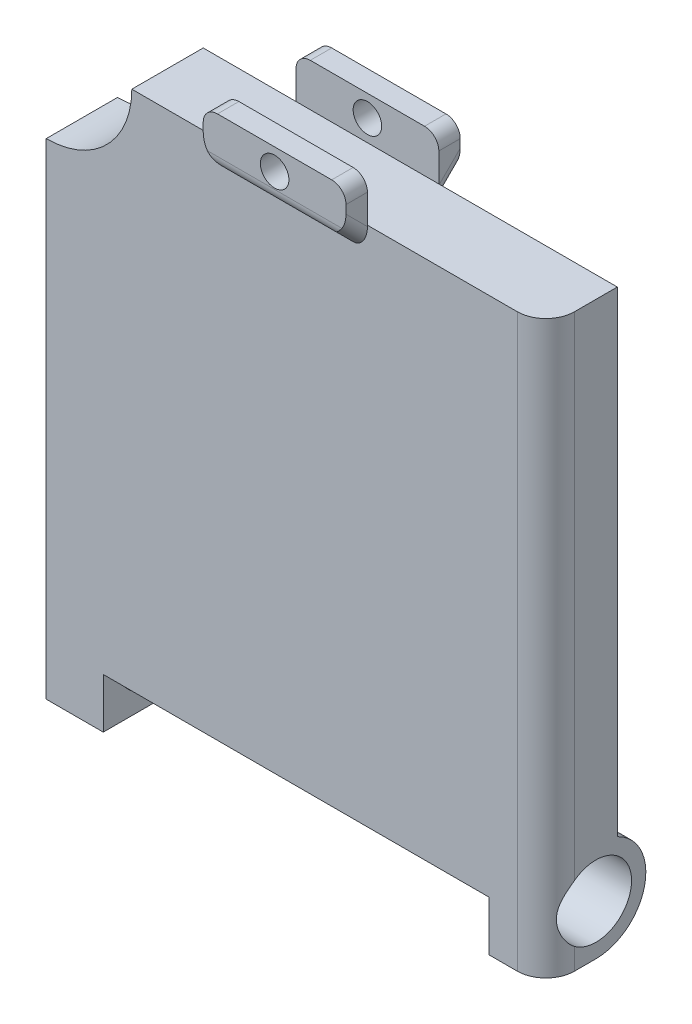
SolidWorks part; units mm, degrees
ref_plane "Front Plane" through (0, 0, 0) normal (0, 0, 1) x (1, 0, 0)
ref_plane "Top Plane" through (0, 0, 0) normal (0, 1, 0) x (1, 0, 0)
ref_plane "Right Plane" through (0, 0, 0) normal (1, 0, 0) x (0, 0, -1)
sketch "Sketch1" plane through (0, 0, 0) normal (0, 0, 1) x (1, 0, 0)
  line L0 (0, 0) -> (0, 36.5)
  line L1 (0, 36.5) -> (35, 36.5)
  line L2 (35, 36.5) -> (35, 0)
  line L3 (35, 0) -> (0, 0)
  dimension "D1" = 36.5
  dimension "D2" = 35
extrude "Boss-Extrude1" add sketch "Sketch1" along normal mid plane 5
sketch "Sketch3" plane through (35, 0, 0) normal (1, 0, 0) x (0, 0, -1)
  line L0 (-2.5, 5.8058) -> (-2.5, 2.251) construction
  line L2 (-2.5, 0) -> (-2.5, 36.5) construction
  line L3 (-2.5, 0) -> (2.5, 0) construction
  circle A0 centre (1, 0) radius 3.5
  dimension "D1" = 7
extrude "Cut-Extrude1" cut sketch "Sketch3" against normal up to surface (35 mm away) up to face at (0, 18.25, 0)
sketch "Sketch4" plane through (35, 0, 0) normal (1, 0, 0) x (0, 0, -1)
  line L0 (-2.5, 0) -> (-2.5, -3.5)
  line L1 (-2.5, -3.5) -> (1, -3.5)
  circle A0 centre (1, 0) radius 3.5
  arc A1 (2.5, 3.1623) -> (-2.5, 0) centre (1, 0) ccw construction
  circle A2 centre (1, 0) radius 2.5
  arc M4 (-2.5, 0) -> (2.5, 3.1623) centre (1, 0) cw
  dimension "D1" = 5
extrude "Boss-Extrude3" add sketch "Sketch4" against normal blind 4 contours A0 A2 M4 | A0 L0 L1 region at (35, -2.7182, 1.7182) region at (35, 2.8744, 0.8179)
ref_plane "Plane2" through (17.5, 0, 0) normal (1, 0, 0) x (0, 0, -1)
mirror "Mirror2" about plane through (17.5, 0, 0) normal (1, 0, 0) of "Boss-Extrude3"
sketch "Sketch5" plane through (17.5, 0, 0) normal (1, 0, 0) x (0, 0, -1)
  line L0 (2.5, 36.5) -> (4, 36.5)
  line L1 (-2.5, 36.5) -> (-4, 36.5)
  line L2 (-4, 36.5) -> (-2.5, 35)
  line L3 (-2.5, -3.5) -> (-2.5, 36.5) construction
  line L4 (4, 36.5) -> (2.5, 35)
  line L5 (2.5, 3.1623) -> (2.5, 36.5) construction
  line L6 (-4, 36.5) -> (-4, 39.5)
  line L7 (-4, 39.5) -> (-2.5, 39.5)
  line L8 (-2.5, 39.5) -> (-2.5, 36.5)
  line L9 (2.5, 36.5) -> (2.5, 39.5)
  line L10 (2.5, 39.5) -> (4, 39.5)
  line L11 (4, 39.5) -> (4, 36.5)
  line L12 (-2.5, 35) -> (-2.5, 36.5)
  line L13 (2.5, 35) -> (2.5, 36.5)
  dimension "D1" = 1.5
  dimension "D2" = 3
extrude "Boss-Extrude4" add sketch "Sketch5" along normal mid plane 10 contours L8 L7 L6 L1 | L2 L12 L1 | L13 L4 L0 | L11 L10 L9 L0 region at (17.5, 38, -3.25) region at (17.5, 36, -3) region at (17.5, 36, 3) region at (17.5, 38, 3.25)
sketch "Sketch6" plane through (0, 0, 4) normal (0, 0, 1) x (1, 0, 0)
  line L0 (17.5, 39.5) -> (17.5, 36.5) construction
  line L1 (22.5, 39.5) -> (12.5, 39.5) construction
  line L2 (22.5, 36.5) -> (12.5, 36.5) construction
  circle A0 centre (17.5, 38) radius 1
  point P8 (17.5, 38)
  dimension "D1" = 2
extrude "Cut-Extrude2" cut sketch "Sketch6" against normal up to surface (8 mm away) up to face at (17.5, 38, -4)
fillet "Fillet1" radius 1 6 edges at (12.5, 35.75, -3.25) (22.5, 35.75, -3.25) (17.5, 36.5, -4) (17.5, 36.5, 4) (12.5, 35.75, 3.25) (22.5, 35.75, 3.25)
fillet "Fillet2" radius 1 4 edges at (12.5, 39.5, -3.25) (12.5, 39.5, 3.25) (22.5, 39.5, -3.25) (22.5, 39.5, 3.25)
sketch "Sketch7" plane through (0, 0, 2.5) normal (0, 0, 1) x (1, 0, 0)
  circle A0 centre (0, 36.5) radius 6
  point P2 (0, 0)
  point P4 (0, 0)
  dimension "D1" = 12
extrude "Cut-Extrude3" cut sketch "Sketch7" against normal up to surface (5 mm away) up to face at (17.5, 25.0743, -2.5)
fillet "Fillet3" radius 2 1 edges at (35, 16.5, 2.5)
